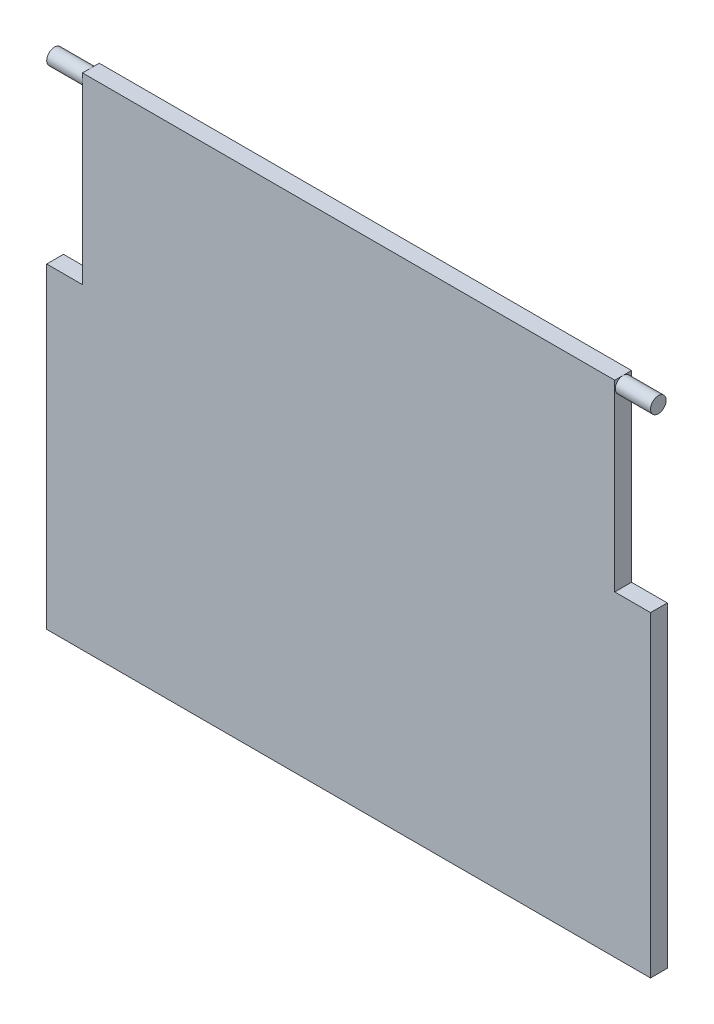
SolidWorks part; units mm, degrees
material "ABS"
ref_plane "Front Plane" through (0, 0, 0) normal (0, 0, 1) x (1, 0, 0)
ref_plane "Top Plane" through (0, 0, 0) normal (0, 1, 0) x (1, 0, 0)
ref_plane "Right Plane" through (0, 0, 0) normal (1, 0, 0) x (0, 0, -1)
sketch "Sketch1" plane through (0, 0, 0) normal (0, 0, 1) x (1, 0, 0)
  line L0 (47.6, 0) -> (50.75, 0)
  line L2 (0, 0) -> (0, -15)
  line L4 (47.6, 0) -> (47.6, -15)
  line L5 (-3.25, 1.4) -> (5.1, 1.4)
  line L6 (-3.25, 1.4) -> (-3.25, 0)
  line L7 (-3.25, 0) -> (0, 0)
  line L8 (50.75, 1.4) -> (50.75, 0)
  line L9 (0, -15) -> (-3.2, -15)
  line L10 (50.8, -43.3) -> (-3.2, -43.3)
  line L11 (50.8, -43.3) -> (50.8, -15)
  line L12 (50.8, -15) -> (47.6, -15)
  line L13 (-3.2, -43.3) -> (-3.2, -15)
  line L14 (42.5, 1.4) -> (50.75, 1.4)
  line L19 (42.5, 1.4) -> (5.1, 1.4)
  point P2 (23.8, -43.3)
  dimension "D1" = 3.2
  dimension "D2" = 54
  dimension "D3" = 1.4
  dimension "D5" = 54
  dimension "D6" = 15
  dimension "D7" = 28.3
  dimension "D9" = 3.2
extrude "Boss-Extrude1" add sketch "Sketch1" along normal blind 1.5 contours L13 L10 L11 L12 L4 L0 L8 L5 L6 L7 L2 L9 region at (23.7984, -21.5071, 0)
sketch "Sketch3" plane through (-3.25, 0, 0) normal (-1, 0, 0) x (0, 0, 1)
  line L0 (0.75, 1.4) -> (0.75, 0) construction
  line L4 (0, 1.4) -> (0, 0)
  line L5 (0, 0) -> (1.5, 0)
  line L6 (1.5, 0) -> (1.5, 1.4)
  line L7 (1.5, 1.4) -> (0, 1.4)
  line L8 (0, 1.4) -> (0, 0)
  line L9 (0, 0) -> (1.5, 0)
  line L10 (1.5, 0) -> (1.5, 1.4)
  line L11 (1.5, 1.4) -> (0, 1.4)
  circle A0 centre (0.75, 0.7) radius 0.7
  line M6 (0, 1.4) -> (0, 0)
  line M7 (0, 0) -> (1.5, 0)
  line M8 (1.5, 0) -> (1.5, 1.4)
  line M9 (1.5, 1.4) -> (0, 1.4)
  dimension "D1" = 0
extrude "Cut-Extrude5" cut sketch "Sketch3" against normal up to surface (3.25 mm away) contours A0 L11 M6 | A0 L10 M9 | A0 L9 M8 | A0 L8 M7 region at (-3.25, 1.3841, 0.375) region at (-3.25, 1.3841, 1.125) up to face at (0, -7.5, 0.75)
extrude "Cut-Extrude6" cut sketch "Sketch3<4>" along direction (1, 0, 0) on the side of the normal up to surface (-50.85 mm away) from surface contours A0 L8 M7 | A0 L11 M6 | A0 L10 M9 | A0 L9 M8 region at (-3.25, 1.3841, 0.375) region at (-3.25, 1.3841, 1.125) up to face at (47.6, -7.5, 0.75) starting at face at (50.75, 0.7, 0.75)
sketch "Sketch3<4>" plane through (-3.25, 0, 0) normal (-1, 0, 0) x (0, 0, 1) same geometry as "Sketch3"
